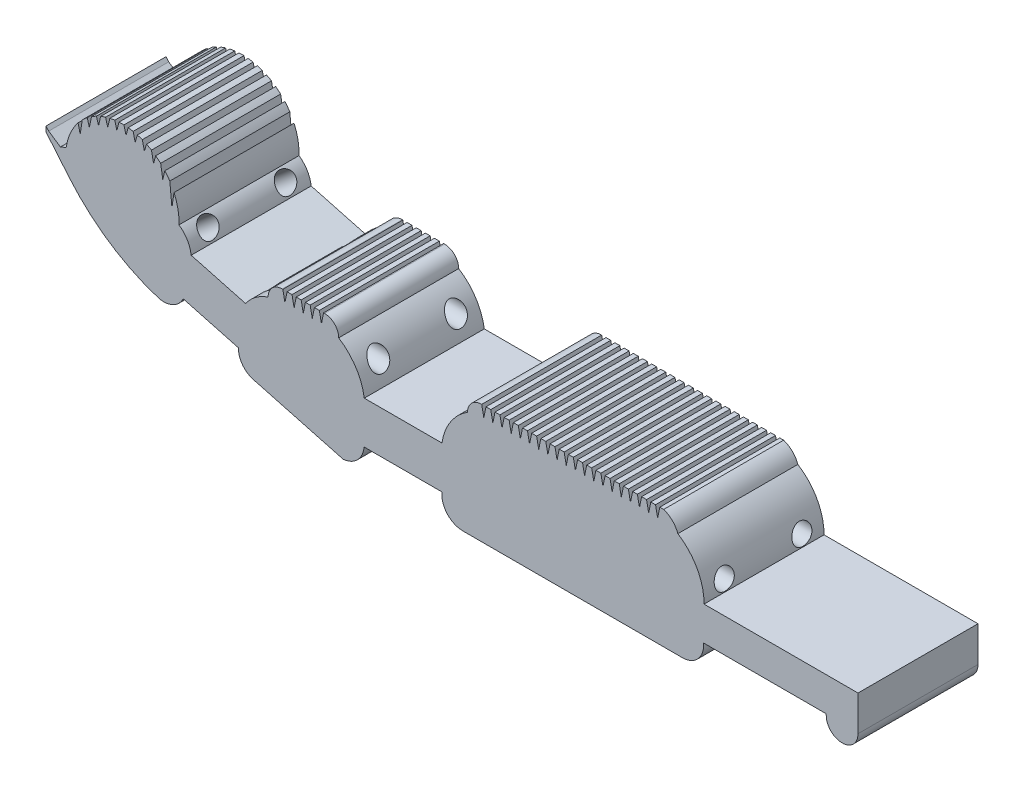
SolidWorks part; units mm, degrees
ref_plane "Front Plane" through (0, 0, 0) normal (0, 0, 1) x (1, 0, 0)
ref_plane "Top Plane" through (0, 0, 0) normal (0, 1, 0) x (1, 0, 0)
ref_plane "Right Plane" through (0, 0, 0) normal (1, 0, 0) x (0, 0, -1)
sketch "Sketch1" plane through (0, 0, 0) normal (0, 0, 1) x (1, 0, 0)
  line L3 (-43.1136, 12.057) -> (-43.4169, 13.5627)
  line L4 (-101.8456, 12.1704) -> (-105.1431, 16.1142)
  line L5 (-105.1431, 16.1142) -> (-105.1431, 16.8503)
  line L6 (-105.1431, 16.8503) -> (-104.7574, 16.4096)
  line L7 (-60.0517, 6) -> (-49.0517, 6)
  line L8 (-49.056, 0) -> (-60.0824, 0)
  line L9 (-71.6764, 13.5872) -> (-71.5925, 13.5872)
  line L10 (-75.5849, 0.3762) -> (-63.0292, -2.9934)
  line L11 (-19.4624, 13.557) -> (-19.7624, 12.057)
  line L12 (-19.7624, 12.057) -> (-20.0624, 13.557)
  line L13 (-20.0624, 13.557) -> (-20.7624, 13.557)
  line L14 (-103.0997, 15.2908) -> (-104.7574, 16.4096)
  line L15 (-20.7624, 13.557) -> (-21.0624, 12.057)
  line L16 (-21.0624, 12.057) -> (-21.3624, 13.557)
  line L17 (-21.3624, 13.557) -> (-22.0363, 13.557)
  line L20 (-22.0363, 13.557) -> (-22.3363, 12.057)
  line L21 (-22.3363, 12.057) -> (-22.6363, 13.557)
  line L22 (-22.6363, 13.557) -> (-23.3363, 13.557)
  line L23 (-23.3363, 13.557) -> (-23.6363, 12.057)
  line L24 (-23.6363, 12.057) -> (-23.9363, 13.557)
  line L25 (-23.9363, 13.557) -> (-24.6363, 13.557)
  line L26 (-24.6363, 13.557) -> (-24.9363, 12.057)
  line L27 (-24.9363, 12.057) -> (-25.2363, 13.557)
  line L28 (-25.2363, 13.557) -> (-25.9363, 13.557)
  line L29 (-25.9363, 13.557) -> (-26.2363, 12.057)
  line L30 (-26.2363, 12.057) -> (-26.5363, 13.557)
  line L31 (-26.5363, 13.557) -> (-27.2363, 13.557)
  line L32 (-27.2363, 13.557) -> (-27.5363, 12.057)
  line L33 (-27.5363, 12.057) -> (-27.8363, 13.557)
  line L34 (-27.8363, 13.557) -> (-28.5363, 13.557)
  line L35 (-28.5363, 13.557) -> (-28.8363, 12.057)
  line L36 (-28.8363, 12.057) -> (-29.1363, 13.557)
  line L37 (-29.1363, 13.557) -> (-29.8363, 13.557)
  line L38 (-29.8363, 13.557) -> (-30.1363, 12.057)
  line L39 (-30.1363, 12.057) -> (-30.4363, 13.557)
  line L40 (-30.4363, 13.557) -> (-31.1363, 13.557)
  line L41 (-31.1363, 13.557) -> (-31.4363, 12.057)
  line L42 (-31.4363, 12.057) -> (-31.7363, 13.557)
  line L43 (-31.7363, 13.557) -> (-32.4363, 13.557)
  line L44 (-32.4363, 13.557) -> (-32.7363, 12.057)
  line L45 (-32.7363, 12.057) -> (-33.0363, 13.557)
  line L46 (-33.0363, 13.557) -> (-33.7363, 13.557)
  line L47 (-33.7363, 13.557) -> (-34.0363, 12.057)
  line L48 (-34.0363, 12.057) -> (-34.3363, 13.557)
  line L49 (-34.3363, 13.557) -> (-35.0363, 13.557)
  line L50 (-35.0363, 13.557) -> (-35.3363, 12.057)
  line L51 (-35.3363, 12.057) -> (-35.6363, 13.557)
  line L52 (-35.6363, 13.557) -> (-36.3363, 13.557)
  line L53 (-36.3363, 13.557) -> (-36.6363, 12.057)
  line L54 (-36.6363, 12.057) -> (-36.9363, 13.557)
  line L55 (-36.9363, 13.557) -> (-37.6363, 13.557)
  line L56 (-37.6363, 13.557) -> (-37.9363, 12.057)
  line L57 (-37.9363, 12.057) -> (-38.2363, 13.557)
  line L58 (-38.2363, 13.557) -> (-38.9363, 13.557)
  line L59 (-38.9363, 13.557) -> (-39.2363, 12.057)
  line L60 (-39.2363, 12.057) -> (-39.5363, 13.557)
  line L61 (-39.5363, 13.557) -> (-40.2363, 13.557)
  line L62 (-40.2363, 13.557) -> (-40.5363, 12.057)
  line L63 (-40.5363, 12.057) -> (-40.8363, 13.557)
  line L64 (-40.8363, 13.557) -> (-41.5363, 13.557)
  line L65 (-41.5363, 13.557) -> (-41.8363, 12.057)
  line L66 (-41.8363, 12.057) -> (-42.1363, 13.557)
  line L67 (-42.1363, 13.557) -> (-42.8103, 13.557)
  line L68 (-42.8103, 13.557) -> (-43.1136, 12.057)
  line L69 (-65.6764, 13.5872) -> (-65.8185, 13.5872)
  line L70 (-65.8185, 13.5872) -> (-66.1185, 12.0872)
  line L71 (-66.1185, 12.0872) -> (-66.4185, 13.5872)
  line L72 (-66.4185, 13.5872) -> (-67.1185, 13.5872)
  line L73 (-67.1185, 13.5872) -> (-67.4185, 12.0872)
  line L74 (-67.4185, 12.0872) -> (-67.7185, 13.5872)
  line L75 (-67.7185, 13.5872) -> (-68.3925, 13.5872)
  line L76 (-68.3925, 13.5872) -> (-68.6925, 12.0872)
  line L77 (-68.6925, 12.0872) -> (-68.9925, 13.5872)
  line L78 (-68.9925, 13.5872) -> (-69.6925, 13.5872)
  line L79 (-69.6925, 13.5872) -> (-69.9925, 12.0872)
  line L80 (-69.9925, 12.0872) -> (-70.2925, 13.5872)
  line L81 (-70.2925, 13.5872) -> (-70.9925, 13.5872)
  line L82 (-70.9925, 13.5872) -> (-71.2925, 12.0872)
  line L83 (-71.2925, 12.0872) -> (-71.5925, 13.5872)
  line L84 (-87.0025, 17.7625) -> (-87.3025, 15.7625)
  line L85 (-87.3025, 15.7625) -> (-87.6025, 18.86)
  line L86 (-88.3025, 19.7805) -> (-88.6025, 18.5805)
  line L87 (-88.6025, 18.5805) -> (-88.9025, 20.3925)
  line L88 (-89.6025, 20.9653) -> (-89.9025, 19.8653)
  line L89 (-89.9025, 19.8653) -> (-90.2025, 21.3624)
  line L90 (-90.9025, 21.7363) -> (-91.2025, 20.7363)
  line L91 (-91.2025, 20.7363) -> (-91.5025, 21.9904)
  line L92 (-92.2025, 22.218) -> (-92.5025, 21.168)
  line L93 (-92.5025, 21.168) -> (-92.8025, 22.3586)
  line L94 (-93.5025, 22.4628) -> (-93.8025, 21.3628)
  line L95 (-93.8025, 21.3628) -> (-94.1025, 22.5027)
  line L96 (-94.8037, 22.4924) -> (-95.1037, 21.3018)
  line L97 (-95.1037, 21.3018) -> (-95.4037, 22.4348)
  line L98 (-96.1015, 22.3097) -> (-96.4015, 21.0526)
  line L99 (-96.4015, 21.0526) -> (-96.7015, 22.1501)
  line L100 (-97.401, 21.8988) -> (-97.701, 20.5988)
  line L101 (-97.701, 20.5988) -> (-98.001, 21.6219)
  line L102 (-98.6991, 21.2189) -> (-98.9991, 19.7189)
  line L103 (-98.9991, 19.7189) -> (-99.2991, 20.791)
  line L104 (-100.0007, 20.1711) -> (-100.3007, 18.2711)
  line L105 (-100.3007, 18.2711) -> (-100.6007, 19.5049)
  line L109 (-84.5776, 11.2737) -> (-76.851, 9.2001)
  line L110 (-85.7196, 5.3678) -> (-77.8789, 3.2637)
  line L113 (-46.028, -3.3091) -> (-15.028, -3.3091)
  line L115 (-30.528, -3.3091) -> (-30.528, 1.6909) construction
  line L116 (-49.0517, 6) -> (-12, 6) construction
  line L117 (-45.427, 11.5872) -> (-12, 11.5872) construction
  line L118 (-30.5258, 7.7582) -> (-30.5258, 24.074) construction
  line L119 (0, 4.8) -> (-11.9164, 4.8)
  line L120 (-18.7884, 13.557) -> (-19.4624, 13.557)
  line L121 (-18.1884, 13.557) -> (-17.6348, 13.557)
  line L122 (-43.4169, 13.5627) -> (-43.4169, 7.7582) construction
  line L123 (-43.4169, 7.7582) -> (-17.6348, 7.7582) construction
  line L124 (-18.1884, 13.557) -> (-18.4884, 12.057)
  line L125 (-18.4884, 12.057) -> (-18.7884, 13.557)
  line L126 (-17.6348, 7.7582) -> (-17.6348, 13.557) construction
  line L127 (-12, 0) -> (0, 0)
  line L132 (0, 4.8) -> (5.3954, 4.8)
  line L133 (0, 4.8) -> (0, 0) construction
  line L135 (0, 2.4) -> (11.9667, 2.4) construction
  line L136 (9.8954, -0.2) -> (9.8954, 4.8)
  line L138 (9.8954, 4.8) -> (5.3954, 4.8)
  line L139 (5.3954, -0.2) -> (5.3954, 0)
  line L140 (5.3954, 0) -> (0, 0)
  line L145 (0, 0) -> (15.2908, 0) construction
  line L146 (7.6454, 0) -> (7.6454, 8) construction
  line L147 (7.6454, -4) -> (7.6454, 0) construction
  line L148 (15.2908, 8) -> (15.2908, 0) construction
  line L149 (0, 8) -> (15.2908, 8) construction
  line L151 (7.6454, -7) -> (7.6454, -4) construction
  line L153 (5.3954, 4.8) -> (5.3954, 5) construction
  arc A0 (-101.8456, 12.1704) -> (-89.2219, 3.7229) centre (-81.0991, 29.5173) ccw
  arc A1 (-43.4169, 13.5627) -> (-44.9427, 12.8796) centre (-43.4403, 11.5694) ccw
  arc A2 (-45.427, 11.5872) -> (-49.0517, 6) centre (-41.1565, 4.8474) ccw
  arc A3 (-44.9427, 12.8796) -> (-45.427, 11.5872) centre (-43.4606, 11.5872) ccw
  arc A4 (-86.3025, 14.1349) -> (-87.0025, 17.7625) centre (-94.3356, 14.4662) ccw
  arc A5 (-87.6025, 18.86) -> (-88.3025, 19.7805) centre (-94.3356, 14.4662) ccw
  arc A6 (-88.9025, 20.3925) -> (-89.6025, 20.9653) centre (-94.3356, 14.4662) ccw
  arc A7 (-49.056, 0) -> (-46.028, -3.3091) centre (-46.072, -0.3094) ccw
  arc A8 (-90.2025, 21.3624) -> (-90.9025, 21.7363) centre (-94.3356, 14.4662) ccw
  arc A9 (-63.0292, -2.9934) -> (-60.0824, 0) centre (-63.3412, 0.261) ccw
  arc A10 (-77.8789, 3.2637) -> (-75.5849, 0.3762) centre (-75.0057, 3.1914) ccw
  arc A12 (-91.5025, 21.9904) -> (-92.2025, 22.218) centre (-94.3356, 14.4662) ccw
  arc A13 (-92.8025, 22.3586) -> (-93.5025, 22.4628) centre (-94.3356, 14.4662) ccw
  arc A15 (-94.1025, 22.5027) -> (-94.8037, 22.4924) centre (-94.3356, 14.4662) ccw
  arc A16 (-89.2219, 3.7229) -> (-85.7196, 5.3678) centre (-88.4454, 6.6207) ccw
  arc A17 (-84.5776, 11.2737) -> (-86.3025, 14.1349) centre (-88.5914, 10.8045) ccw
  arc A18 (-73.6764, 11.5872) -> (-76.851, 9.2001) centre (-71.7747, 5.7536) ccw
  arc A19 (-60.0517, 6) -> (-63.6764, 11.5872) centre (-67.9469, 4.8474) ccw
  arc A20 (-63.6764, 11.5872) -> (-65.6764, 13.5872) centre (-65.6764, 11.5872) ccw
  arc A21 (-71.6764, 13.5872) -> (-73.6764, 11.5872) centre (-71.6764, 11.5872) ccw
  arc A22 (-102.2903, 15.6336) -> (-103.0997, 15.2908) centre (-95.7741, -0.8806) ccw
  arc A24 (-95.4037, 22.4348) -> (-96.1015, 22.3097) centre (-94.3356, 14.4662) ccw
  arc A26 (-96.7015, 22.1501) -> (-97.401, 21.8988) centre (-94.3356, 14.4662) ccw
  arc A27 (-98.001, 21.6219) -> (-98.6991, 21.2189) centre (-94.3356, 14.4662) ccw
  arc A30 (-99.2991, 20.791) -> (-100.0007, 20.1711) centre (-94.3356, 14.4662) ccw
  arc A38 (-100.6007, 19.5049) -> (-102.2903, 15.6336) centre (-94.3356, 14.4662) ccw
  arc A40 (-12, 0) -> (-15.028, -3.3091) centre (-14.984, -0.3094) cw
  arc A41 (-15.6247, 11.5872) -> (-17.6348, 13.557) centre (-18.6728, 10.4872) ccw
  arc A42 (-15.6247, 11.5872) -> (-11.9164, 4.8) centre (-19.8952, 4.8474) cw
  arc A46 (5.3954, 5) -> (9.8954, 5) centre (7.6454, 5) cw construction
  arc A47 (5.3954, -0.2) -> (9.8954, -0.2) centre (7.6454, -0.2) ccw
  point P86 (-29.6483, 15.1731)
  dimension "D3" = 6
  dimension "D4" = 6
  dimension "D8" = 11
  dimension "D9" = 8
  dimension "D10" = 18.0933
  dimension "D11" = 20.0133
  dimension "D12" = 31
  dimension "D13" = 3.6247
  dimension "D14" = 5
  dimension "D15" = 5.6348
  dimension "D16" = 5.6348
  dimension "D17" = 4.8
  dimension "D19" = 12
  dimension "D20" = 11.9164
  dimension "D21" = 11.0264
  dimension "D22" = 8.1181
extrude "Boss-Extrude1" add sketch "Sketch1" along normal blind 17
ref_plane "Plane1" through (-60, 0, 0) normal (1, 0, 0) x (0, 0, -1)
sketch "Sketch2" plane through (-60, 0, 0) normal (1, 0, 0) x (0, 0, -1)
  line L0 (-17, 6) -> (0, 6) construction
  line L1 (0, 6) -> (0, 11.5872) construction
  line L2 (-17, 6) -> (-17, 11.5872) construction
  line L3 (-17, 11.5872) -> (0, 11.5872) construction
  line L4 (-17, 8.7936) -> (0, 8.7936) construction
  line L5 (-8.5, 11.5872) -> (-8.5, 6) construction
  circle A0 centre (-14, 8.7936) radius 1.4
  circle A2 centre (-3, 8.7936) radius 1.4
  dimension "D1" = 2.8
  dimension "D2" = 3
extrude "Cut-Extrude1" cut sketch "Sketch2" against normal blind 12 and the other way blind 40
sketch "Sketch3" plane through (0, 0, 0) normal (1, 0, 0) x (0, 0, -1)
  line L0 (-17, 4.8) -> (0, 4.8) construction
  line L1 (-14, 4.8) -> (-14, 6.3) construction
  line L2 (-8.5, 4.8) -> (-8.5, 11.5872) construction
  line L3 (-17, 11.5872) -> (0, 11.5872) construction
  line L4 (-17, 4.8) -> (-17, 11.5872) construction
  circle A0 centre (-14, 6.3) radius 1.4
  circle A2 centre (-3, 6.3) radius 1.4
  dimension "D2" = 2.8
  dimension "D1" = 1.5
  dimension "D3" = 3
extrude "Cut-Extrude2" cut sketch "Sketch3" against normal blind 42
ref_plane "Plane2" through (-70.8015, 25.8008, 0) normal (0.9396, -0.3424, 0) x (0, 0, -1)
sketch "Sketch4" plane through (-70.8015, 25.8008, 0) normal (0.9396, -0.3424, 0) x (0, 0, -1)
  line L0 (-8.5, -14.3388) -> (-8.5, -17.6686) construction
  line L1 (0, -16.0037) -> (-17, -16.0037) construction
  line L5 (0, -17.6686) -> (-17, -17.6686) construction
  line L6 (-17, -17.6686) -> (-17, -14.3388) construction
  line L7 (-17, -14.3388) -> (0, -14.3388) construction
  line L8 (0, -14.3388) -> (0, -17.6686) construction
  circle A0 centre (-3, -16.0037) radius 1.4
  circle A2 centre (-14, -16.0037) radius 1.4
  dimension "D1" = 2.8
  dimension "D2" = 3
extrude "Cut-Extrude3" cut sketch "Sketch4" along normal blind 12
ref_plane "Plane3" through (-44.1141, -36.9869, 0) normal (0.7663, 0.6425, 0) x (0, 0, -1)
sketch "Sketch5" plane through (-44.1141, -36.9869, 0) normal (0.7663, 0.6425, 0) x (0, 0, -1)
  line L0 (-17, 66.28) -> (0, 66.28) construction
  line L1 (0, 66.28) -> (0, 62.9792) construction
  line L2 (-17, 62.9792) -> (0, 62.9792) construction
  line L3 (0, 62.9792) -> (0, 66.28) construction
  line L4 (0, 62.9792) -> (-17, 62.9792) construction
  line L5 (-17, 62.9792) -> (-17, 66.28) construction
  line L6 (-17, 64.6296) -> (0, 64.6296) construction
  line L7 (-8.5, 66.28) -> (-8.5, 62.9792) construction
  circle A0 centre (-14, 64.6296) radius 1.4
  circle A1 centre (-3, 64.6296) radius 1.4
  dimension "D1" = 2.8
  dimension "D2" = 3
extrude "Cut-Extrude4" cut sketch "Sketch5" against normal blind 12 and the other way blind 12
